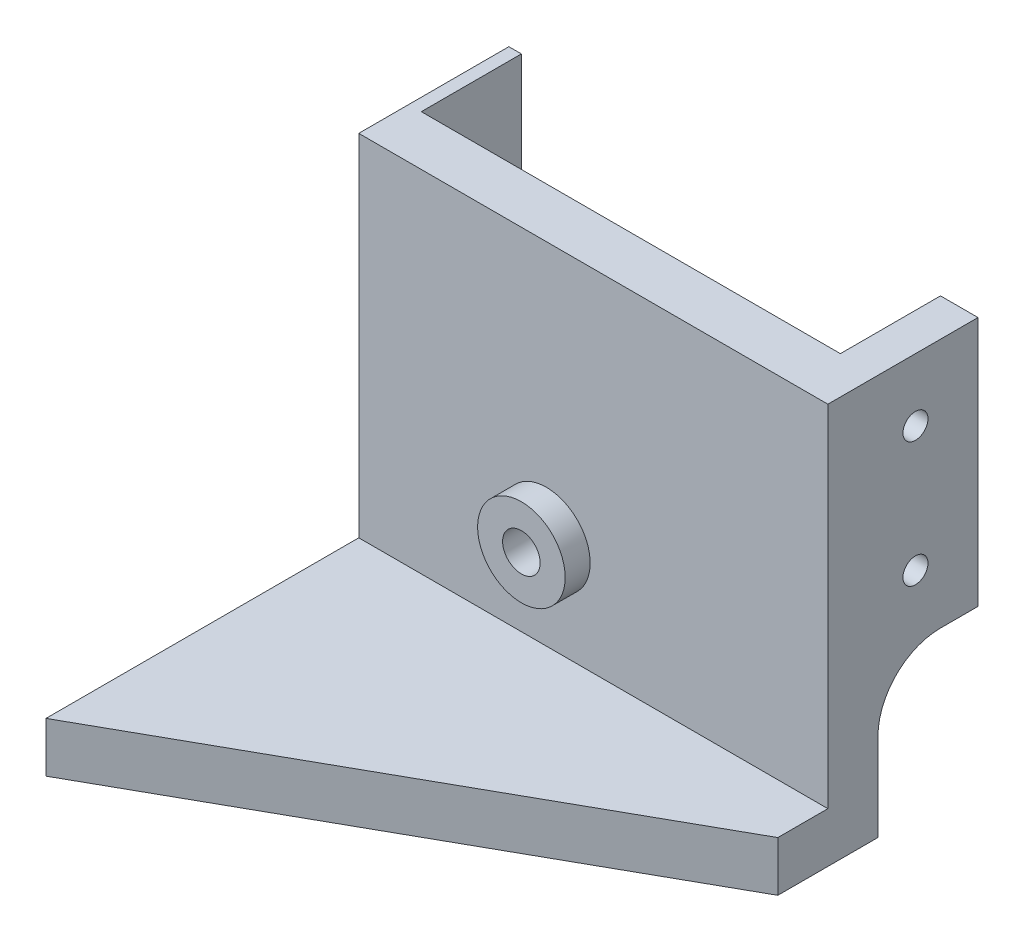
SolidWorks part; units mm, degrees
ref_plane "Front Plane" through (0, 0, 0) normal (0, 0, 1) x (1, 0, 0)
ref_plane "Top Plane" through (0, 0, 0) normal (0, 1, 0) x (1, 0, 0)
ref_plane "Right Plane" through (0, 0, 0) normal (1, 0, 0) x (0, 0, -1)
sketch "Sketch1" plane through (0, 0, 0) normal (0, 1, 0) x (1, 0, 0)
  line L1 (0, 0) -> (37.5, 0)
  line L2 (0, 0) -> (0, 12)
  line L3 (0, 12) -> (37.5, 12)
  line L4 (37.5, 0) -> (37.5, 12)
  line L5 (1, 12) -> (34.5, 12)
  line L6 (1, 12) -> (1, 4)
  line L7 (1, 4) -> (34.5, 4)
  line L8 (34.5, 12) -> (34.5, 4)
  dimension "D1" = 12
  dimension "D2" = 37.5
  dimension "D3" = 33.5
  dimension "D4" = 1
  dimension "10" = 8
extrude "Boss-Extrude1" add sketch "Sketch1" along normal blind 20 contours L3 L8 L7 L6 L2 L1 L4 region at (20.2225, 0, -3.0549)
sketch "Sketch2" plane through (0, 0, 0) normal (0, -1, 0) x (1, 0, 0)
  line L0 (37.5, 0) -> (37.5, -12) construction
  line L1 (0, 0) -> (37.5, 0)
  line L2 (0, 0) -> (0, -4)
  line L3 (0, -4) -> (37.5, -4)
  line L4 (37.5, 0) -> (37.5, -4)
extrude "Boss-Extrude2" add sketch "Sketch2" along normal blind 12
fillet "Fillet1" radius 5 2 edges at (0.5, 0, -4) (36, 0, -4)
sketch "Sketch3" plane through (0, 0, 0) normal (0, 0, 1) x (1, 0, 0)
  line L0 (37.5, 20) -> (37.5, -12) construction
  line L1 (0, -12) -> (37.5, -12)
  line L2 (0, -12) -> (0, -8)
  line L3 (0, -8) -> (37.5, -8)
  line L4 (37.5, -12) -> (37.5, -8)
  dimension "D1" = 4
extrude "Boss-Extrude3" add sketch "Sketch3" along normal blind 25 contours L3 L4 L1 L2
sketch "Sketch4" plane through (0, 0, 0) normal (0, 0, 1) x (1, 0, 0)
  line L0 (0, -8) -> (37.5, -8) construction
  line L1 (0, 20) -> (0, -8) construction
  circle A0 centre (15, -0.5) radius 1.5
  circle A1 centre (15, -0.5) radius 3.5
  dimension "D1" = 3
  dimension "D2" = 7.5
  dimension "D4" = 15
  dimension "D3" = 2
extrude "Boss-Extrude4" add sketch "Sketch4" along normal blind 2
sketch "Sketch5" plane through (0, 0, 2) normal (0, 0, 1) x (1, 0, 0)
  circle A0 centre (15, -0.5) radius 1.5 construction
  circle A1 centre (15, -0.5) radius 1.5
extrude "Cut-Extrude1" cut sketch "Sketch5" against normal through all contours A1
sketch "Sketch6" plane through (0, -8, 0) normal (0, 1, 0) x (1, 0, 0)
  line L0 (0, -25) -> (37.5, -4)
  line L1 (37.5, -25) -> (37.5, 0) construction
  line L2 (37.5, -4) -> (37.5, -25)
  line L3 (37.5, -25) -> (0, -25)
  dimension "D1" = 4
extrude "Cut-Extrude2" cut sketch "Sketch6" against normal blind 10
sketch "Sketch7" plane through (0, 0, 0) normal (-1, 0, 0) x (0, 0, 1)
  line L0 (-12, 20) -> (-12, 0) construction
  line L1 (0, 20) -> (-12, 20) construction
  line L2 (-9, 0) -> (-12, 0) construction
  circle A0 centre (-7, 15) radius 1
  circle A1 centre (-7, 5) radius 1
  dimension "D1" = 2
  dimension "D3" = 5
  dimension "D2" = 5
  dimension "D4" = 10
  dimension "D5" = 5
extrude "Cut-Extrude3" cut sketch "Sketch7" against normal through all both and the other way through all
